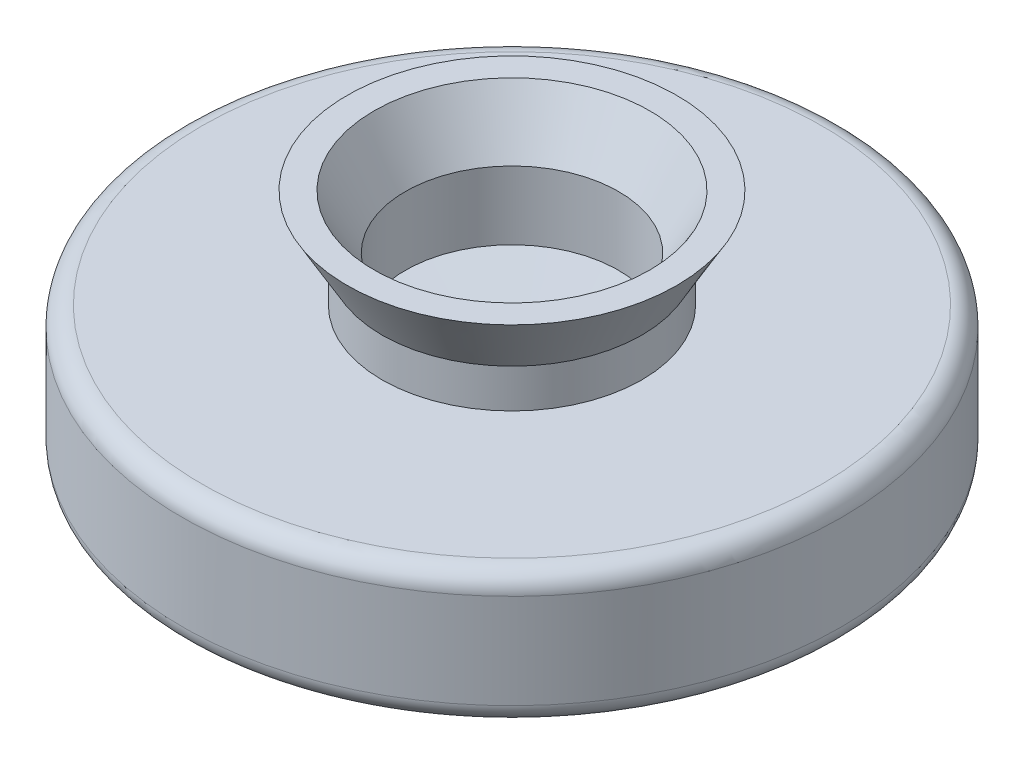
SolidWorks part; units mm, degrees
ref_plane "Front Plane" through (0, 0, 0) normal (0, 0, 1) x (1, 0, 0)
ref_plane "Top Plane" through (0, 0, 0) normal (0, 1, 0) x (1, 0, 0)
ref_plane "Right Plane" through (0, 0, 0) normal (1, 0, 0) x (0, 0, -1)
sketch "Sketch1" plane through (0, 0, 0) normal (0, 0, 1) x (1, 0, 0)
  line L1 (0, -201655.0005) -> (0, 281095.0265) construction
  line L2 (80.4576, 0) -> (27.5, 0) construction
  line L3 (4.2164, -22.4115) -> (4.2164, -28.4115)
  line L5 (85, 6) -> (33.5, 6)
  line L6 (33.5, 6) -> (33.5, 16)
  line L8 (79, 0) -> (27.5, 0)
  line L9 (27.5, 0) -> (27.5, 17.6077)
  line L15 (0, -1021.2131) -> (0, 48978.7869) construction
  line L19 (33.5, 16) -> (42.5, 31.5885)
  line L20 (42.5, 31.5885) -> (35.5718, 31.5885)
  line L22 (27.5, 0) -> (27.5, 94) construction
  line L23 (33.5, 6) -> (33.5, 94) construction
  line L24 (35.5718, 31.5885) -> (27.5, 17.6077)
  line L25 (80.4576, 6) -> (33.5, 6) construction
  line L26 (4.2164, -28.4115) -> (85, -28.4115)
  line L27 (85, -28.4115) -> (85, 6)
  line L28 (4.2164, -22.4115) -> (69.7846, -17.2512)
  line L29 (79, -7.282) -> (79, 0)
  arc A0 (79, -7.282) -> (69.7846, -17.2512) centre (69, -7.282) cw
  point P8 (79, -14.2526)
  point P10 (79, 4.3193)
  dimension "D6" = 10
  dimension "D9" = 30
  dimension "D12" = 6
  dimension "D14" = 60
  dimension "D13" = 27.5
  dimension "D15" = 10
  dimension "D2" = 85
  dimension "D8" = 42.5
  dimension "8.4328/2" = 4.2164
  dimension "D5" = 6
  dimension "D4" = 6
  dimension "D7" = 4.5
  dimension "D3" = 6
revolve "Revolve2" add sketch "Sketch1" angle 360 about L15
sketch "Sketch2" plane through (0, 0, 0) normal (0, 0, 1) x (1, 0, 0)
  line L1 (0, -22.6761) -> (81.4732, -22.6761)
  line L2 (81.4732, -22.6761) -> (81.4732, -18.432)
  line L6 (0, -7.8102) -> (81.4732, -7.8102)
  line L8 (81.4732, -7.8102) -> (81.4732, -18.432)
  line L9 (0, -201021.2131) -> (0, 248978.7869) construction
  line L10 (0, -7.8102) -> (0, -22.6761)
  point P2 (0, -22.6761)
  point P4 (80.1101, -9.3459)
  point P6 (81.4732, -7.8102)
revolve "Revolve4" [suppressed] add sketch "Sketch2" angle 360 about L15
other "Intersect1" [suppressed]
fillet "Fillet1" radius 5 2 edges at (85, 6, 0) (85, -28.4115, 0)
equation "\"D12@Sketch1\"=\"D3@Sketch1\""
equation "\"D5@Sketch1\"=\"D3@Sketch1\""
equation "\"D4@Sketch1\"=\"D3@Sketch1\""
